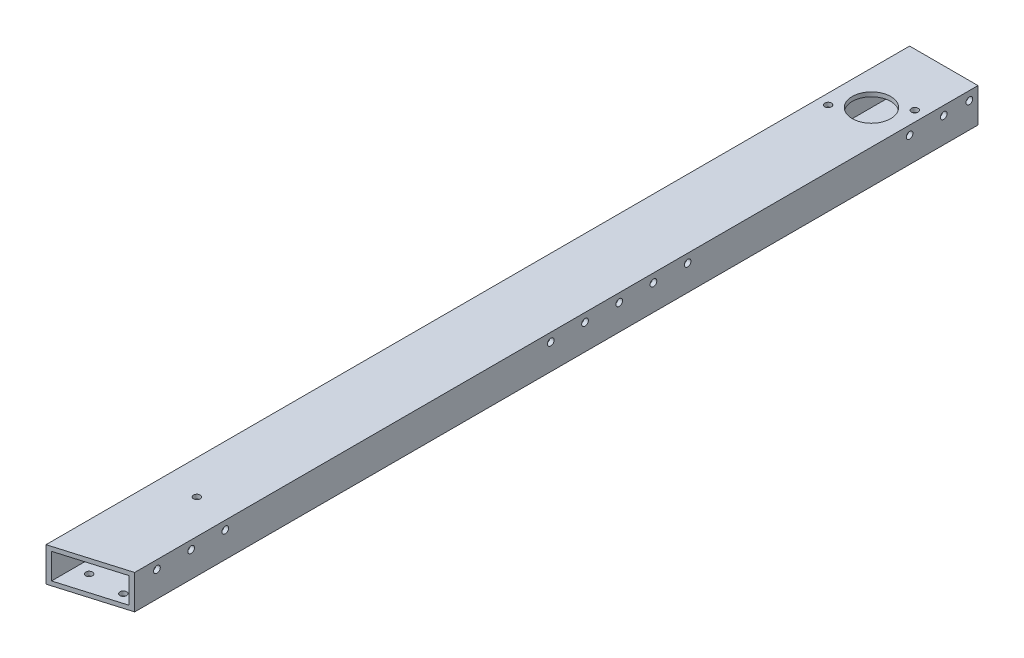
SolidWorks part; units mm, degrees
ref_plane "Front Plane" through (0, 0, 0) normal (0, 0, 1) x (1, 0, 0)
ref_plane "Top Plane" through (0, 0, 0) normal (0, 1, 0) x (1, 0, 0)
ref_plane "Right Plane" through (0, 0, 0) normal (1, 0, 0) x (0, 0, -1)
sketch "Sketch1" plane through (0, 0, 0) normal (0, 0, 1) x (1, 0, 0)
  line L0 (-22.225, 9.525) -> (22.225, 9.525)
  line L2 (-25.4, 12.7) -> (25.4, 12.7)
  line L3 (-25.4, 12.7) -> (-25.4, -12.7)
  line L4 (-25.4, -12.7) -> (25.4, -12.7)
  line L5 (25.4, 12.7) -> (25.4, -12.7)
  line L10 (22.225, 9.525) -> (22.225, -9.525)
  line L11 (-22.225, -9.525) -> (22.225, -9.525)
  line L12 (-22.225, 9.525) -> (-22.225, -9.525)
  point P12 (0, 12.7)
  point P14 (25.4, 0)
  dimension "Wall Thickness" = 3.175
  dimension "Outside Width" = 50.8
  dimension "Outside Height" = 25.4
  dimension "Inside Height" = 19.05
  dimension "Inside Width" = 44.45
sketch "Sketch2" plane through (0, 0, 0) normal (1, 0, 0) x (0, 0, -1)
  line L0 (320.675, 0) -> (-320.675, 0)
  point P4 (0, 0)
  point P7 (-320.675, 0)
  point P10 (320.675, 0)
  dimension "Length" = 641.35
sketch "Sketch3" plane through (0, 0, 0) normal (0, 0, 1) x (1, 0, 0)
  line L21 (25.4, 12.7) -> (-25.4, 12.7)
  line L22 (25.4, -12.7) -> (25.4, 12.7)
  line L23 (-25.4, -12.7) -> (25.4, -12.7)
  line L24 (-25.4, 12.7) -> (-25.4, -12.7)
  line L25 (25.4, 12.7) -> (-25.4, 12.7)
  line L26 (25.4, -12.7) -> (25.4, 12.7)
  line L27 (-25.4, -12.7) -> (25.4, -12.7)
  line L28 (-25.4, 12.7) -> (-25.4, -12.7)
  line L29 (22.225, 9.525) -> (-22.225, 9.525)
  line L30 (22.225, -9.525) -> (22.225, 9.525)
  line L31 (-22.225, -9.525) -> (22.225, -9.525)
  line L32 (-22.225, 9.525) -> (-22.225, -9.525)
  line L33 (22.225, 9.525) -> (-22.225, 9.525)
  line L34 (22.225, -9.525) -> (22.225, 9.525)
  line L35 (-22.225, -9.525) -> (22.225, -9.525)
  line L36 (-22.225, 9.525) -> (-22.225, -9.525)
  dimension "D1" = 0
  dimension "D2" = 0
extrude "Boss-Extrude1" add sketch "Sketch3" along normal up to vertex (320.675 mm away) and the other way up to vertex (320.675 mm away) up to point (0, 0, 320.675) other way up to point (0, 0, -320.675)
sketch "Drawing Reference" plane through (0, 0, 0) normal (1, 0, 0) x (0, 0, -1)
  line L0 (-320.675, 0) -> (320.675, 0) construction
  line L1 (0, -12.7) -> (0, 12.7) construction
  line L2 (-320.675, -12.7) -> (320.675, -12.7) construction
  line L5 (-320.675, 12.7) -> (320.675, 12.7) construction
  point P7 (-284.099, 0)
  point P8 (284.099, 0)
  dimension "D1" = 36.576
sketch "Sketch4" plane through (0, 12.7, 0) normal (0, 1, 0) x (1, 0, 0)
  line L0 (-25.4, -320.675) -> (25.4, -305.6274)
  line L1 (25.4, -320.675) -> (25.4, 320.675) construction
  line L2 (25.4, -320.675) -> (-25.4, -320.675)
  dimension "D1" = 16.5
extrude "Cut-Extrude1" cut sketch "Sketch4" against normal through all and the other way through all flip side to cut
sketch "Sketch8" plane through (0, 12.7, 0) normal (0, 1, 0) x (1, 0, 0)
  line L0 (0, 320.675) -> (0, 266.954) construction
  line L1 (25.4, 320.675) -> (-25.4, 320.675) construction
  circle A0 centre (0, 266.954) radius 14.2875
  dimension "D1" = 53.721
extrude "Cut-Extrude2" cut sketch "Sketch8" against normal through all
sketch "Sketch9" plane through (0, -12.7, 0) normal (0, -1, 0) x (1, 0, 0)
  line L0 (-12.7762, 284.753) -> (-12.7762, 301.263) construction
  line L1 (-12.7762, 301.263) -> (12.6238, 301.263) construction
  line L2 (12.6238, 301.263) -> (12.6238, 284.753) construction
  line L3 (12.6238, 284.753) -> (-12.7762, 284.753) construction
hole_wizard "#10 Clearance Hole1" positions "Sketch10" profile "Sketch11" hole size "#10" standard "ANSI Inch"
sketch "Sketch10" plane through (0, -12.7, 0) normal (0, -1, 0) x (-1, 0, 0)
  point P0 (-12.6238, -284.753)
  point P3 (12.7762, -284.753)
  point P6 (12.7762, -301.263)
  point P9 (-12.6238, -301.263)
sketch "Sketch11" plane through (12.6238, -12.7, 284.753) normal (1, 0, 0) x (0, 0, -1)
  line L0 (0, 0) -> (0, 6.5757)
  line L1 (0, 6.5757) -> (2.4892, 5.08)
  line L2 (2.4892, 5.08) -> (2.4892, 0)
  line L5 (2.4892, 0) -> (0, 0)
  line L10 (0, 6.5757) -> (-2.4892, 5.08) construction
  line L11 (0, -6.35) -> (0, 107.95) construction
  dimension "Hole Dia." = 4.9784
  dimension "Hole Depth" = 5.08
  dimension "Drill Angle" = 118
sketch "Sketch12" plane through (25.4, 0, 0) normal (1, 0, 0) x (0, 0, -1)
  line L0 (320.675, 533.4) -> (-305.6274, 533.4) construction
  line L1 (320.675, 520.7) -> (320.675, 546.1) construction
  line L2 (-305.6274, 546.1) -> (-305.6274, 520.7) construction
hole_wizard "#10 Clearance Hole2" positions "Sketch13" profile "Sketch14" hole size "#10" standard "ANSI Inch"
sketch "Sketch13" plane through (25.4, 0, 0) normal (1, 0, 0) x (0, 0, -1)
  point P0 (314.2868, 6.1483)
  point P3 (295.2368, 6.1483)
  point P6 (269.875, 6.1483)
sketch "Sketch14" plane through (25.4, 6.1483, -314.2868) normal (0, 1, 0) x (0, 0, -1)
  line L0 (0, 0) -> (0, 4.7977)
  line L1 (0, 4.7977) -> (2.4892, 3.302)
  line L2 (2.4892, 3.302) -> (2.4892, 0)
  line L5 (2.4892, 0) -> (0, 0)
  line L10 (0, 4.7977) -> (-2.4892, 3.302) construction
  line L11 (0, -6.35) -> (0, 107.95) construction
  dimension "Hole Dia." = 4.9784
  dimension "Hole Depth" = 3.302
  dimension "Drill Angle" = 118
hole_wizard "#10 Clearance Hole3" positions "Sketch15" profile "Sketch16" hole size "#10" standard "ANSI Inch" end condition through all
sketch "Sketch15" plane through (25.4, 0, 0) normal (1, 0, 0) x (0, 0, -1)
  point P0 (105.029, 6.35)
  point P3 (79.629, 6.35)
  point P6 (54.229, 6.35)
  point P9 (28.829, 6.35)
  point P12 (3.429, 6.35)
  point P24 (-289.0885, 6.3882)
  point P27 (-263.6885, 6.3882)
  point P30 (-238.3267, 6.3882)
sketch "Sketch16" plane through (25.4, 6.35, -105.029) normal (0, 1, 0) x (0, 0, -1)
  line L0 (0, 0) -> (0, 50.8)
  line L1 (0, 50.8) -> (2.4892, 50.8)
  line L2 (2.4892, 50.8) -> (2.4892, 0)
  line L5 (2.4892, 0) -> (0, 0)
  line L11 (0, -6.35) -> (0, 107.95) construction
  dimension "Thru Hole Dia." = 4.9784
  dimension "Thru Hole Depth" = 50.8
sketch "Sketch18" plane through (0, 12.7, 0) normal (0, 1, 0) x (1, 0, 0)
  line L0 (17.786, 281.371) -> (-17.786, 252.537) construction
hole_wizard "#10 Clearance Hole4" positions "Sketch19" profile "Sketch20" hole size "#10" standard "ANSI Inch" end condition through all
sketch "Sketch19" plane through (0, 12.7, 0) normal (0, 1, 0) x (1, 0, 0)
  point P0 (-17.786, 252.537)
  point P3 (17.786, 281.371)
sketch "Sketch20" plane through (-17.786, 12.7, -252.537) normal (1, 0, 0) x (0, 0, 1)
  line L0 (0, 0) -> (0, 25.4)
  line L1 (0, 25.4) -> (5.2197, 25.4)
  line L2 (2.4892, 22.2589) -> (2.4892, 0)
  line L5 (2.4892, 0) -> (0, 0)
  line L7 (5.2197, 25.4) -> (2.4892, 22.2589)
  line L8 (-5.2197, 25.4) -> (-2.4892, 22.2589) construction
  line L11 (0, -6.35) -> (0, 107.95) construction
  dimension "Thru Hole Dia." = 4.9784
  dimension "Thru Hole Depth" = 25.4
  dimension "Far C'Sink Dia." = 10.4394
  dimension "Far C'Sink Angle" = 82
sketch "Sketch21" plane through (0, 12.7, 0) normal (0, 1, 0) x (1, 0, 0)
  line L0 (-0.0762, -284.753) -> (-0.0762, -233.953) construction
  line L1 (12.6238, -284.753) -> (-12.7762, -284.753) construction
  dimension "D1" = 50.8
hole_wizard "#10 Clearance Hole5" positions "Sketch22" profile "Sketch23" hole size "#10" standard "ANSI Inch" end condition through all
sketch "Sketch22" plane through (0, 12.7, 0) normal (0, 1, 0) x (1, 0, 0)
  point P0 (-0.0762, -233.953)
sketch "Sketch23" plane through (-0.0762, 12.7, 233.953) normal (1, 0, 0) x (0, 0, 1)
  line L0 (0, 0) -> (0, 25.4)
  line L1 (0, 25.4) -> (2.4892, 25.4)
  line L2 (2.4892, 25.4) -> (2.4892, 0)
  line L5 (2.4892, 0) -> (0, 0)
  line L11 (0, -6.35) -> (0, 107.95) construction
  dimension "Thru Hole Dia." = 4.9784
  dimension "Thru Hole Depth" = 25.4
equation "\"D1@Drawing Reference\"=\"Outside Width@Sketch1\" * 0.72"
